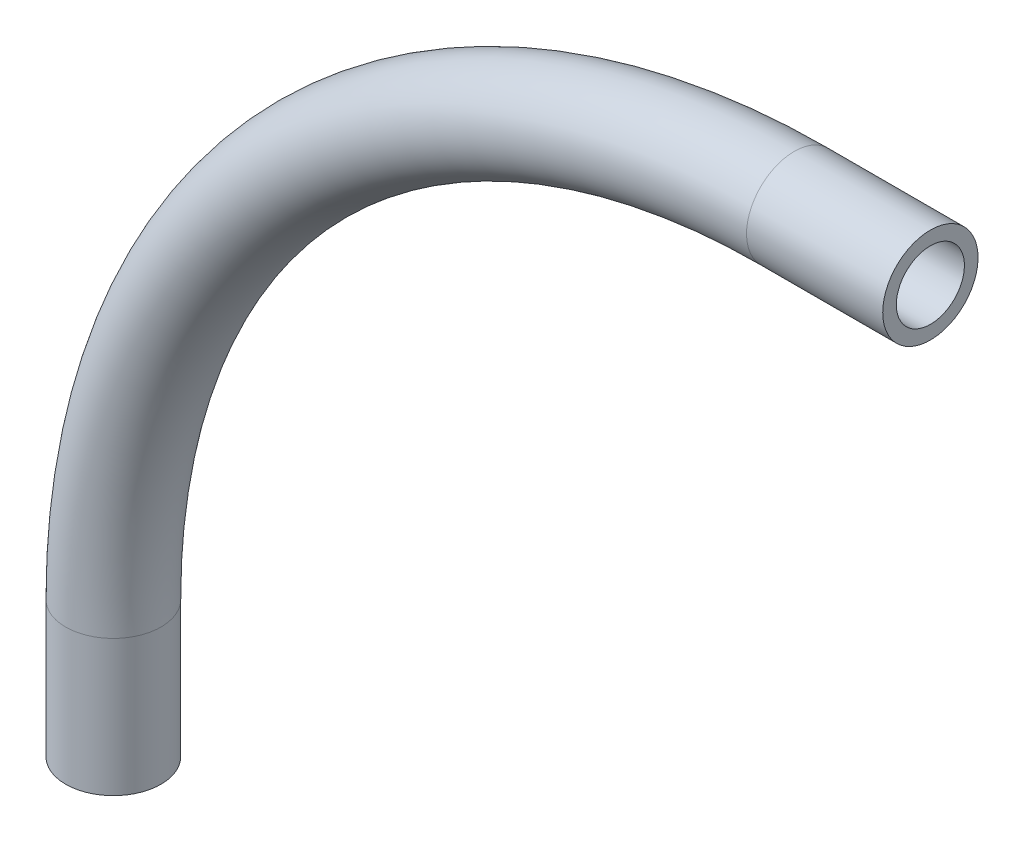
SolidWorks part; units mm, degrees
ref_plane "Front Plane" through (0, 0, 0) normal (0, 0, 1) x (1, 0, 0)
ref_plane "Top Plane" through (0, 0, 0) normal (0, 1, 0) x (1, 0, 0)
ref_plane "Right Plane" through (0, 0, 0) normal (1, 0, 0) x (0, 0, -1)
sketch "Sketch1" plane through (0, 0, 0) normal (0, 0, 1) x (1, 0, 0)
  line L2 (0, 50) -> (10, 50)
  line L3 (-50, 0) -> (-50, -10)
  arc A0 (0, 50) -> (-50, 0) centre (0, 0) ccw
  dimension "D1" = 50
  dimension "D2" = 10
  dimension "D3" = 10
sweep "Sweep1" add path "Sketch1" circular profile diameter 7 parameters "D3"=7
sweep "Cut-Sweep1" cut path "Sketch1<2>" circular profile diameter 5 parameters "D3"=5
sketch "Sketch1<2>" plane through (0, 0, 0) normal (0, 0, 1) x (1, 0, 0) same geometry as "Sketch1"
